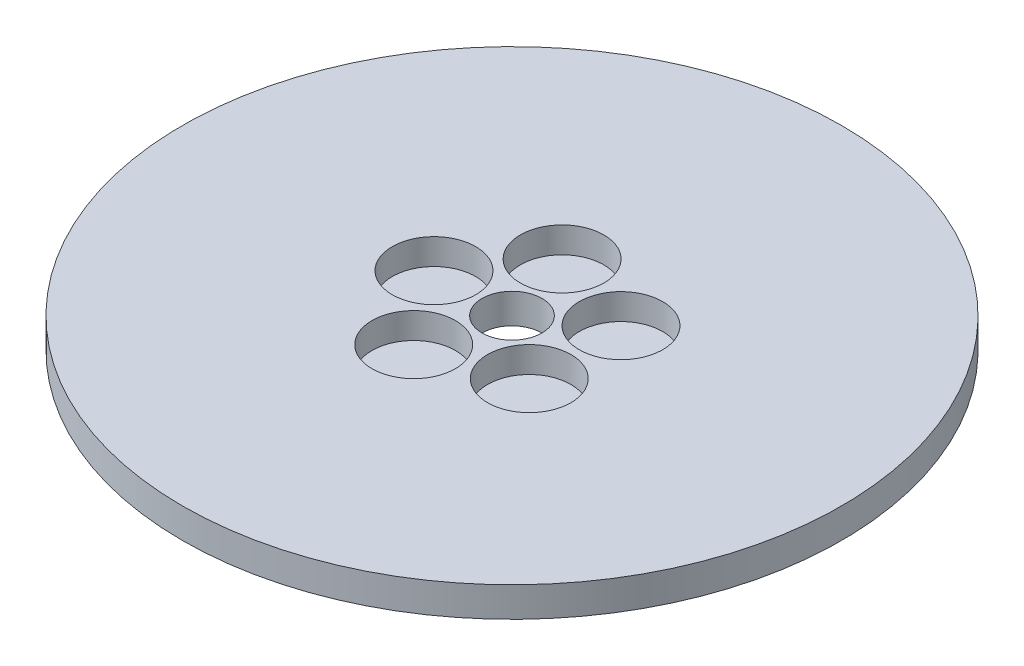
SolidWorks part; units mm, degrees
ref_plane "Front Plane" through (0, 0, 0) normal (0, 0, 1) x (1, 0, 0)
ref_plane "Top Plane" through (0, 0, 0) normal (0, 1, 0) x (1, 0, 0)
ref_plane "Right Plane" through (0, 0, 0) normal (1, 0, 0) x (0, 0, -1)
sketch "Sketch1" plane through (0, 0, 0) normal (0, 1, 0) x (1, 0, 0)
  circle A0 centre (0, 0) radius 55
  dimension "FLANGE_OD" = 110
extrude "Boss-Extrude1" add sketch "Sketch1" along normal blind 5
sketch "Sketch2" plane through (0, 0, 0) normal (0, 1, 0) x (1, 0, 0)
  circle A0 centre (0, 0) radius 5
  dimension "BORE_D" = 10
extrude "Cut-Extrude1" cut sketch "Sketch2" along normal through all
sketch "Sketch3" plane through (0, 5, 0) normal (0, 1, 0) x (1, 0, 0)
  circle A0 centre (0, 0) radius 13.019 construction
  circle A1 centre (-13.019, 0) radius 6.963
  dimension "BOLT_D" = 13.926
  dimension "BOLT_PCD" = 26.038
extrude "Cut-Extrude2" cut sketch "Sketch3" against normal blind 4.3276
pattern_circular "CirPattern1" count 5 over 360 about axis through (0, 0, 0) along (0, 1, 0) of "Cut-Extrude2"
